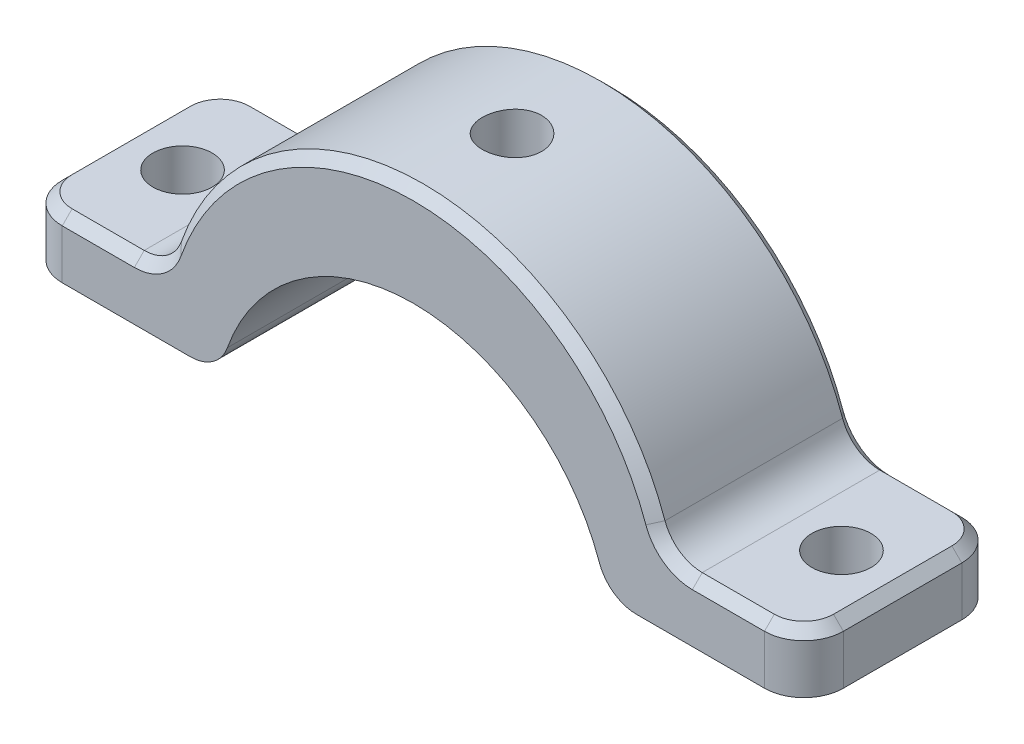
SolidWorks part; units mm, degrees
material "2024 合金"
ref_plane "前视基准面" through (0, 0, 0) normal (0, 0, 1) x (1, 0, 0)
ref_plane "上视基准面" through (0, 0, 0) normal (0, 1, 0) x (1, 0, 0)
ref_plane "右视基准面" through (0, 0, 0) normal (1, 0, 0) x (0, 0, -1)
sketch "草图1" plane through (0, 0, 0) normal (0, 0, 1) x (1, 0, 0)
  line L0 (-19.798, 0) -> (-19.798, 3)
  line L1 (-19.798, 3) -> (-14.1421, 3)
  line L2 (0, 0) -> (0, 34.7368) construction
  line L3 (-19.798, 0) -> (19.798, 0) construction
  line L4 (0, 0) -> (0, -18.9474) construction
  line L5 (-19.798, 0) -> (-11.3137, 0)
  line L6 (19.798, 0) -> (11.3137, 0)
  line L7 (19.798, 3) -> (14.1421, 3)
  line L8 (19.798, 0) -> (19.798, 3)
  arc A0 (-12.2565, 4.3333) -> (12.2565, 4.3333) centre (0, 0) cw
  arc A1 (-9.4281, 1.3333) -> (9.4281, 1.3333) centre (0, -2) cw
  arc A2 (-14.1421, 3) -> (-12.2565, 4.3333) centre (-14.1421, 5) ccw
  arc A3 (-9.4281, 1.3333) -> (-11.3137, 0) centre (-11.3137, 2) cw
  arc A4 (9.4281, 1.3333) -> (11.3137, 0) centre (11.3137, 2) ccw
  arc A5 (14.1421, 3) -> (12.2565, 4.3333) centre (14.1421, 5) cw
  point P9 (9.798, 0)
  point P15 (-9.798, 0)
  dimension "D2" = 13
  dimension "D3" = 2
  dimension "D1" = 10
  dimension "D6" = 2
  dimension "D7" = 2
  dimension "D4" = 6
  dimension "D5" = 10
extrude "凸台-拉伸1" add sketch "草图1" along normal blind 10
fillet "圆角1" radius 2 4 edges at (-19.798, 1.5, 0) (-19.798, 1.5, 10) (19.798, 1.5, 10) (19.798, 1.5, 0)
chamfer "倒角1" distance 0.5 angle 45 16 edges at (15.97, 3, 10) (19.2122, 3, 9.4142) (12.9874, 3.367, 10) (19.798, 3, 5) (0, 13, 10) (19.2122, 3, 0.5858) (-12.9874, 3.367, 10) (15.97, 3, 0) (-15.97, 3, 10) (12.9874, 3.367, 0) (-19.2122, 3, 9.4142) (0, 13, 0) (-19.798, 3, 5) (-12.9874, 3.367, 0) (-19.2122, 3, 0.5858) (-15.97, 3, 0)
sketch "草图2" plane through (0, 3, 0) normal (0, 1, 0) x (1, 0, 0)
  line L0 (-16.7, -5) -> (16.7, -5) construction
  line L1 (0, 0) -> (0, -32.6302) construction
  circle A0 centre (-16.7, -5) radius 1.5
  circle A1 centre (16.7, -5) radius 1.5
  dimension "D1" = 3
  dimension "D2" = 3
  dimension "D3" = 16.7
  dimension "D4" = 5
extrude "切除-拉伸1" cut sketch "草图2" against normal through all
sketch "草图3" plane through (0, 0, 0) normal (0, -1, 0) x (1, 0, 0)
  line L0 (0, 5) -> (0, 0) construction
  circle A0 centre (0, 5) radius 1.5
  dimension "D1" = 3
  dimension "D2" = 5
extrude "切除-拉伸2" cut sketch "草图3" against normal through all
